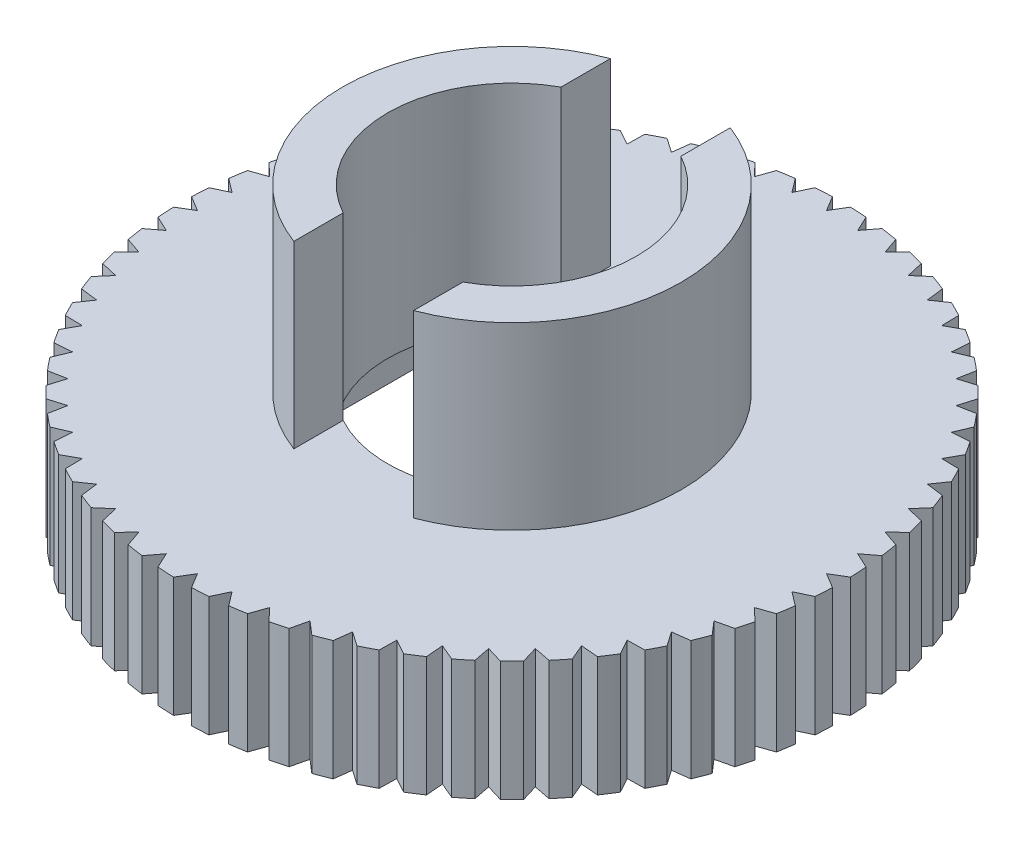
SolidWorks part; units mm, degrees
ref_plane "前视基准面" through (0, 0, 0) normal (0, 0, 1) x (1, 0, 0)
ref_plane "上视基准面" through (0, 0, 0) normal (0, 1, 0) x (1, 0, 0)
ref_plane "右视基准面" through (0, 0, 0) normal (1, 0, 0) x (0, 0, -1)
sketch "草图1" plane through (0, 0, 0) normal (0, 1, 0) x (1, 0, 0)
  circle A0 centre (0, 0) radius 5.65
  circle A1 centre (0, 0) radius 11
  circle A2 centre (0, 0) radius 4.15
  dimension "D1" = 11.3
  dimension "D2" = 22
  dimension "D3" = 1.5
extrude "凸台-拉伸1" add sketch "草图1" along normal blind 10 contours A0 A2 region at (-5.4902, 0, 0)
extrude "凸台-拉伸2" add sketch "草图1<3>" along normal blind 4 contours A1 A0 region at (-10.6889, 0, 0)
sketch "草图1<3>" plane through (0, 0, 0) normal (0, 1, 0) x (1, 0, 0) same geometry as "草图1"
sketch "草图2" plane through (0, 0, 0) normal (0, -1, 0) x (1, 0, 0)
  line L0 (-6, -3.4641) -> (-6, 3.4641) construction
  line L1 (-6, 3.4641) -> (0, 6.9282) construction
  line L2 (0, 6.9282) -> (6, 3.4641) construction
  line L3 (6, 3.4641) -> (6, -3.4641) construction
  line L4 (6, -3.4641) -> (0, -6.9282) construction
  line L5 (0, -6.9282) -> (-6, -3.4641) construction
  line L6 (0, -7.2746) -> (-6.3, -3.6373)
  line L7 (-6.3, -3.6373) -> (-6.3, 3.6373)
  line L8 (-6.3, 3.6373) -> (0, 7.2746)
  line L9 (0, 7.2746) -> (6.3, 3.6373)
  line L10 (6.3, 3.6373) -> (6.3, -3.6373)
  line L11 (6.3, -3.6373) -> (0, -7.2746)
  circle A0 centre (0, 0) radius 6.9282 construction
  dimension "D1" = 12
  dimension "D2" = 0.3
extrude "切除-拉伸1" cut sketch "草图2" against normal blind 2.9
sketch "草图3" plane through (0, 4, 0) normal (0, 1, 0) x (1, 0, 0)
  line L0 (0, -11) -> (0, -10.5) construction
  line L1 (0, -10.5) -> (0.3, -10.9959)
  line L2 (0, -10.5) -> (-0.3, -10.9959)
  circle A0 centre (0, 0) radius 11 construction
  arc A1 (-0.3, -10.9959) -> (0.3, -10.9959) centre (0, 0) ccw
  arc A2 (0.3, -10.9959) -> (-0.3, -10.9959) centre (0, 0) ccw construction
  dimension "D1" = 0.5
  dimension "D2" = 0.3
extrude "切除-拉伸2" cut sketch "草图3" against normal up to surface (4 mm away) up to face at (0, 0, 0)
pattern_circular "阵列(圆周)1" count 60 over 360 about axis through (0, 4, 0) along (0, 1, 0) of "切除-拉伸2"
sketch "草图4" plane through (0, 10, 0) normal (0, 1, 0) x (1, 0, 0)
  line L0 (0, 4.1459) -> (0, 5.647) construction
  line L1 (-2, 5.2842) -> (-2, 3.6363)
  line L2 (2, 5.2842) -> (2, 3.6363)
  line L3 (2, -3.6363) -> (2, -5.2842)
  line L4 (-2, -3.6363) -> (-2, -5.2842)
  circle A0 centre (0, 0) radius 4.15 construction
  circle A1 centre (0, 0) radius 5.65 construction
  circle A2 centre (0, 0) radius 5.65 construction
  arc A3 (-2, -3.6363) -> (2, -3.6363) centre (0, 0) ccw
  arc A4 (-2, -5.2842) -> (2, -5.2842) centre (0, 0) ccw
  arc A5 (-2, 5.2842) -> (-2, -5.2842) centre (0, 0) ccw construction
  arc A6 (-2, 3.6363) -> (-2, -3.6363) centre (0, 0) ccw construction
  arc A7 (2, -5.2842) -> (2, 5.2842) centre (0, 0) ccw construction
  arc A8 (2, 5.2842) -> (-2, 5.2842) centre (0, 0) ccw
  arc A9 (2, -3.6363) -> (2, 3.6363) centre (0, 0) ccw construction
  arc A10 (2, 3.6363) -> (-2, 3.6363) centre (0, 0) ccw
  dimension "D1" = 2
  dimension "D2" = 2
extrude "切除-拉伸3" cut sketch "草图4" against normal up to surface (6 mm away) up to face at (0, 4, 0)
